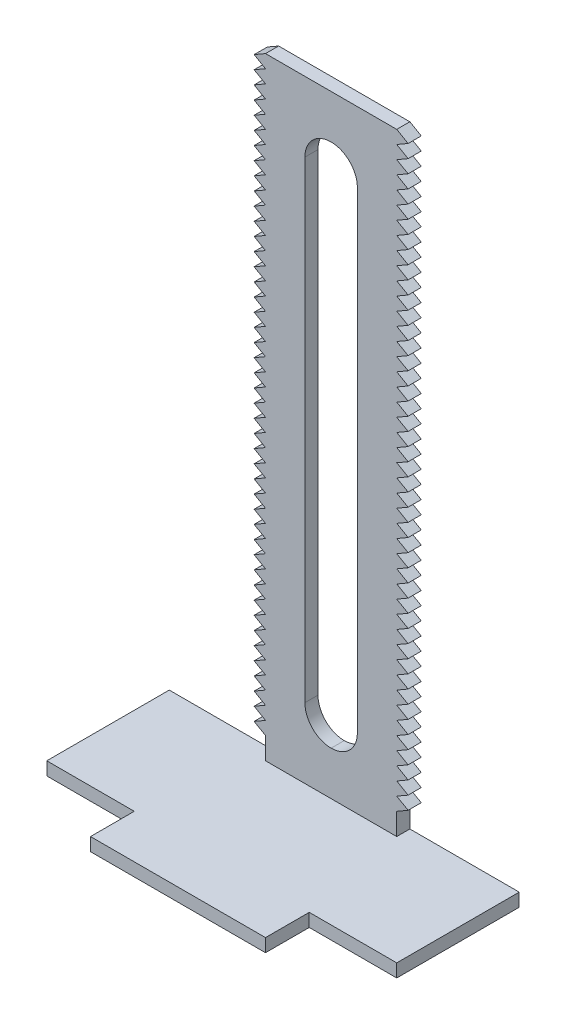
SolidWorks part; units mm, degrees
ref_plane "Front Plane" through (0, 0, 0) normal (0, 0, 1) x (1, 0, 0)
ref_plane "Top Plane" through (0, 0, 0) normal (0, 1, 0) x (1, 0, 0)
ref_plane "Right Plane" through (0, 0, 0) normal (1, 0, 0) x (0, 0, -1)
sketch "Sketch2" plane through (0, 0, 0) normal (0, 1, 0) x (1, 0, 0)
  line L1 (-15, 1.5) -> (15, 1.5)
  line L2 (-15, 1.5) -> (-15, -1.5)
  line L3 (-15, -1.5) -> (15, -1.5)
  line L4 (15, 1.5) -> (15, -1.5)
  line L5 (-15, 1.5) -> (15, -1.5) construction
  line L6 (-15, -1.5) -> (15, 1.5) construction
  point P0 (0, 0)
  dimension "D1" = 30
  dimension "D2" = 3
extrude "Boss-Extrude1" add sketch "Sketch2" along normal blind 110
sketch "Sketch3" plane through (0, 0, 1.5) normal (0, 0, 1) x (1, 0, 0)
  line L0 (15, 110) -> (17.5981, 108.5)
  line L1 (17.5981, 108.5) -> (15, 107)
  line L2 (15, 110) -> (15, 0) construction
  line L3 (15, 107) -> (15, 110)
  line L4 (15, 110) -> (15, 107)
  line L5 (15, 104) -> (15, 107)
  line L6 (17.5981, 105.5) -> (15, 104)
  line L7 (15, 107) -> (17.5981, 105.5)
  line L8 (15, 101) -> (15, 104)
  line L9 (17.5981, 102.5) -> (15, 101)
  line L10 (15, 104) -> (17.5981, 102.5)
  line L11 (15, 98) -> (15, 101)
  line L12 (17.5981, 99.5) -> (15, 98)
  line L13 (15, 101) -> (17.5981, 99.5)
  line L14 (15, 95) -> (15, 98)
  line L15 (17.5981, 96.5) -> (15, 95)
  line L16 (15, 98) -> (17.5981, 96.5)
  line L17 (15, 92) -> (15, 95)
  line L18 (17.5981, 93.5) -> (15, 92)
  line L19 (15, 95) -> (17.5981, 93.5)
  line L20 (15, 89) -> (15, 92)
  line L21 (17.5981, 90.5) -> (15, 89)
  line L22 (15, 92) -> (17.5981, 90.5)
  line L23 (15, 86) -> (15, 89)
  line L24 (17.5981, 87.5) -> (15, 86)
  line L25 (15, 89) -> (17.5981, 87.5)
  line L26 (15, 83) -> (15, 86)
  line L27 (17.5981, 84.5) -> (15, 83)
  line L28 (15, 86) -> (17.5981, 84.5)
  line L29 (15, 80) -> (15, 83)
  line L30 (17.5981, 81.5) -> (15, 80)
  line L31 (15, 83) -> (17.5981, 81.5)
  line L32 (15, 77) -> (15, 80)
  line L33 (17.5981, 78.5) -> (15, 77)
  line L34 (15, 80) -> (17.5981, 78.5)
  line L35 (15, 74) -> (15, 77)
  line L36 (17.5981, 75.5) -> (15, 74)
  line L37 (15, 77) -> (17.5981, 75.5)
  line L38 (15, 71) -> (15, 74)
  line L39 (17.5981, 72.5) -> (15, 71)
  line L40 (15, 74) -> (17.5981, 72.5)
  line L41 (15, 68) -> (15, 71)
  line L42 (17.5981, 69.5) -> (15, 68)
  line L43 (15, 71) -> (17.5981, 69.5)
  line L44 (15, 65) -> (15, 68)
  line L45 (17.5981, 66.5) -> (15, 65)
  line L46 (15, 68) -> (17.5981, 66.5)
  line L47 (15, 62) -> (15, 65)
  line L48 (17.5981, 63.5) -> (15, 62)
  line L49 (15, 65) -> (17.5981, 63.5)
  line L50 (15, 59) -> (15, 62)
  line L51 (17.5981, 60.5) -> (15, 59)
  line L52 (15, 62) -> (17.5981, 60.5)
  line L53 (15, 56) -> (15, 59)
  line L54 (17.5981, 57.5) -> (15, 56)
  line L55 (15, 59) -> (17.5981, 57.5)
  line L56 (15, 53) -> (15, 56)
  line L57 (17.5981, 54.5) -> (15, 53)
  line L58 (15, 56) -> (17.5981, 54.5)
  line L59 (15, 50) -> (15, 53)
  line L60 (17.5981, 51.5) -> (15, 50)
  line L61 (15, 53) -> (17.5981, 51.5)
  line L62 (15, 47) -> (15, 50)
  line L63 (17.5981, 48.5) -> (15, 47)
  line L64 (15, 50) -> (17.5981, 48.5)
  line L65 (15, 44) -> (15, 47)
  line L66 (17.5981, 45.5) -> (15, 44)
  line L67 (15, 47) -> (17.5981, 45.5)
  line L68 (15, 41) -> (15, 44)
  line L69 (17.5981, 42.5) -> (15, 41)
  line L70 (15, 44) -> (17.5981, 42.5)
  line L71 (15, 38) -> (15, 41)
  line L72 (17.5981, 39.5) -> (15, 38)
  line L73 (15, 41) -> (17.5981, 39.5)
  line L74 (15, 35) -> (15, 38)
  line L75 (17.5981, 36.5) -> (15, 35)
  line L76 (15, 38) -> (17.5981, 36.5)
  line L77 (-15, 110) -> (-15, 0) construction
  line L78 (-15, 110) -> (-17.5981, 108.5)
  line L79 (-17.5981, 108.5) -> (-15, 107)
  line L80 (-15, 107) -> (-15, 110)
  line L81 (-17.5981, 105.5) -> (-15, 104)
  line L82 (-15, 107) -> (-17.5981, 105.5)
  line L83 (-15, 104) -> (-15, 107)
  line L84 (-17.5981, 102.5) -> (-15, 101)
  line L85 (-15, 104) -> (-17.5981, 102.5)
  line L86 (-15, 101) -> (-15, 104)
  line L87 (-17.5981, 99.5) -> (-15, 98)
  line L88 (-15, 101) -> (-17.5981, 99.5)
  line L89 (-15, 98) -> (-15, 101)
  line L90 (-17.5981, 96.5) -> (-15, 95)
  line L91 (-15, 98) -> (-17.5981, 96.5)
  line L92 (-15, 95) -> (-15, 98)
  line L93 (-17.5981, 93.5) -> (-15, 92)
  line L94 (-15, 95) -> (-17.5981, 93.5)
  line L95 (-15, 92) -> (-15, 95)
  line L96 (-17.5981, 90.5) -> (-15, 89)
  line L97 (-15, 92) -> (-17.5981, 90.5)
  line L98 (-15, 89) -> (-15, 92)
  line L99 (-17.5981, 87.5) -> (-15, 86)
  line L100 (-15, 89) -> (-17.5981, 87.5)
  line L101 (-15, 86) -> (-15, 89)
  line L102 (-17.5981, 84.5) -> (-15, 83)
  line L103 (-15, 86) -> (-17.5981, 84.5)
  line L104 (-15, 83) -> (-15, 86)
  line L105 (-17.5981, 81.5) -> (-15, 80)
  line L106 (-15, 83) -> (-17.5981, 81.5)
  line L107 (-15, 80) -> (-15, 83)
  line L108 (-17.5981, 78.5) -> (-15, 77)
  line L109 (-15, 80) -> (-17.5981, 78.5)
  line L110 (-15, 77) -> (-15, 80)
  line L111 (-17.5981, 75.5) -> (-15, 74)
  line L112 (-15, 77) -> (-17.5981, 75.5)
  line L113 (-15, 74) -> (-15, 77)
  line L114 (-17.5981, 72.5) -> (-15, 71)
  line L115 (-15, 74) -> (-17.5981, 72.5)
  line L116 (-15, 71) -> (-15, 74)
  line L117 (-17.5981, 69.5) -> (-15, 68)
  line L118 (-15, 71) -> (-17.5981, 69.5)
  line L119 (-15, 68) -> (-15, 71)
  line L120 (-17.5981, 66.5) -> (-15, 65)
  line L121 (-15, 68) -> (-17.5981, 66.5)
  line L122 (-15, 65) -> (-15, 68)
  line L123 (-17.5981, 63.5) -> (-15, 62)
  line L124 (-15, 65) -> (-17.5981, 63.5)
  line L125 (-15, 62) -> (-15, 65)
  line L126 (-17.5981, 60.5) -> (-15, 59)
  line L127 (-15, 62) -> (-17.5981, 60.5)
  line L128 (-15, 59) -> (-15, 62)
  line L129 (-17.5981, 57.5) -> (-15, 56)
  line L130 (-15, 59) -> (-17.5981, 57.5)
  line L131 (-15, 56) -> (-15, 59)
  line L132 (-17.5981, 54.5) -> (-15, 53)
  line L133 (-15, 56) -> (-17.5981, 54.5)
  line L134 (-15, 53) -> (-15, 56)
  line L135 (-17.5981, 51.5) -> (-15, 50)
  line L136 (-15, 53) -> (-17.5981, 51.5)
  line L137 (-15, 50) -> (-15, 53)
  line L138 (-17.5981, 48.5) -> (-15, 47)
  line L139 (-15, 50) -> (-17.5981, 48.5)
  line L140 (-15, 47) -> (-15, 50)
  line L141 (-17.5981, 45.5) -> (-15, 44)
  line L142 (-15, 47) -> (-17.5981, 45.5)
  line L143 (-15, 44) -> (-15, 47)
  line L144 (-17.5981, 42.5) -> (-15, 41)
  line L145 (-15, 44) -> (-17.5981, 42.5)
  line L146 (-15, 41) -> (-15, 44)
  line L147 (-17.5981, 39.5) -> (-15, 38)
  line L148 (-15, 41) -> (-17.5981, 39.5)
  line L149 (-15, 38) -> (-15, 41)
  line L150 (-17.5981, 36.5) -> (-15, 35)
  line L151 (-15, 38) -> (-17.5981, 36.5)
  line L152 (-15, 35) -> (-15, 38)
  line L153 (-17.5981, 33.5) -> (-15, 32)
  line L154 (-15, 35) -> (-17.5981, 33.5)
  line L155 (-15, 32) -> (-15, 35)
  line L156 (17.5981, 33.5) -> (15, 32)
  line L157 (15, 32) -> (15, 35)
  line L158 (15, 35) -> (17.5981, 33.5)
  line L159 (-17.5981, 30.5) -> (-15, 29)
  line L160 (-15, 32) -> (-17.5981, 30.5)
  line L161 (-15, 29) -> (-15, 32)
  line L162 (17.5981, 30.5) -> (15, 29)
  line L163 (15, 29) -> (15, 32)
  line L164 (15, 32) -> (17.5981, 30.5)
  line L165 (-17.5981, 27.5) -> (-15, 26)
  line L166 (-15, 29) -> (-17.5981, 27.5)
  line L167 (-15, 26) -> (-15, 29)
  line L168 (17.5981, 27.5) -> (15, 26)
  line L169 (15, 26) -> (15, 29)
  line L170 (15, 29) -> (17.5981, 27.5)
  line L171 (-17.5981, 24.5) -> (-15, 23)
  line L172 (-15, 26) -> (-17.5981, 24.5)
  line L173 (-15, 23) -> (-15, 26)
  line L174 (17.5981, 24.5) -> (15, 23)
  line L175 (15, 23) -> (15, 26)
  line L176 (15, 26) -> (17.5981, 24.5)
  line L177 (-17.5981, 21.5) -> (-15, 20)
  line L178 (-15, 23) -> (-17.5981, 21.5)
  line L179 (-15, 20) -> (-15, 23)
  line L180 (17.5981, 21.5) -> (15, 20)
  line L181 (15, 20) -> (15, 23)
  line L182 (15, 23) -> (17.5981, 21.5)
  line L183 (-17.5981, 18.5) -> (-15, 17)
  line L184 (-15, 20) -> (-17.5981, 18.5)
  line L185 (-15, 17) -> (-15, 20)
  line L186 (17.5981, 18.5) -> (15, 17)
  line L187 (15, 17) -> (15, 20)
  line L188 (15, 20) -> (17.5981, 18.5)
  line L189 (-17.5981, 15.5) -> (-15, 14)
  line L190 (-15, 17) -> (-17.5981, 15.5)
  line L191 (-15, 14) -> (-15, 17)
  line L192 (17.5981, 15.5) -> (15, 14)
  line L193 (15, 14) -> (15, 17)
  line L194 (15, 17) -> (17.5981, 15.5)
  line L195 (-17.5981, 12.5) -> (-15, 11)
  line L196 (-15, 14) -> (-17.5981, 12.5)
  line L197 (-15, 11) -> (-15, 14)
  line L198 (17.5981, 12.5) -> (15, 11)
  line L199 (15, 11) -> (15, 14)
  line L200 (15, 14) -> (17.5981, 12.5)
  line L201 (-17.5981, 9.5) -> (-15, 8)
  line L202 (-15, 11) -> (-17.5981, 9.5)
  line L203 (-15, 8) -> (-15, 11)
  line L204 (17.5981, 9.5) -> (15, 8)
  line L205 (15, 8) -> (15, 11)
  line L206 (15, 11) -> (17.5981, 9.5)
  line L207 (-17.5981, 6.5) -> (-15, 5)
  line L208 (-15, 8) -> (-17.5981, 6.5)
  line L209 (-15, 5) -> (-15, 8)
  line L210 (17.5981, 6.5) -> (15, 5)
  line L211 (15, 5) -> (15, 8)
  line L212 (15, 8) -> (17.5981, 6.5)
  line M152 (15, 0) -> (15, 110)
  line M154 (-15, 110) -> (-15, 0)
  dimension "D1" = 3
  dimension "D2" = 3
  dimension "D3" = 3
  dimension "D5" = 30
  dimension "D6" = 2.5981
  dimension "D7" = 3
  dimension "D8" = 3
  dimension "D9" = 3
  dimension "D11" = 30
  dimension "D12" = 2.5981
  dimension "D14" = 2.5981
  dimension "D4" = 25
  dimension "D10" = 25
  dimension "D13" = 11
extrude "Boss-Extrude2" add sketch "Sketch3" against normal blind 3 contours L78 L79 M154 | L82 L81 M154 | L85 L84 M154 | L88 L87 M154 | L91 L90 M154 | L94 L93 M154 | L97 L96 M154 | L100 L99 M154 | L103 L102 M154 | L106 L105 M154 | L109 L108 M154 | L1 L0 M152 | L7 L6 M152 | L10 L9 M152 | L13 L12 M152 | L16 L15 M152 | L19 L18 M152 | L22 L21 M152 | L25 L24 M152 | L28 L27 M152 | L31 L30 M152 | L34 L33 M152 | L112 L111 M154 | L115 L114 M154 | L118 L117 M154 | L121 L120 M154 | L124 L123 M154 | L127 L126 M154 | L130 L129 M154 | L133 L132 M154 | L136 L135 M154 | L139 L138 M154 | L142 L141 M154 | L145 L144 M154 | L148 L147 M154 | L151 L150 M154 | L37 L36 M152 | L43 L42 M152 | L46 L45 M152 | L49 L48 M152 | L61 L60 M152 | L64 L63 M152 | L67 L66 M152 | L70 L69 M152 | L73 L72 M152 | L158 L156 M152 | L164 L162 M152 | L154 L153 M154 | L160 L159 M154 | L166 L165 M154 | L172 L171 M154 | L178 L177 M154 | L184 L183 M154 | L170 L168 M152 | L176 L174 M152 | L190 L189 M154 | L182 L180 M152 | L188 L186 M152 | L196 L195 M154 | L194 L192 M152 | L200 L198 M152 | L206 L204 M152 | L212 L210 M152 | L208 L207 M154 | L202 L201 M154 | L40 L39 L38 | L52 L51 L50 | L55 L54 L53 | L58 L57 L56 | L76 L75 L74 region at (15.866, 6.5, 1.5) region at (15.866, 9.5, 1.5) region at (15.866, 12.5, 1.5) region at (15.866, 15.5, 1.5) region at (15.866, 18.5, 1.5) region at (15.866, 21.5, 1.5) region at (15.866, 24.5, 1.5) region at (15.866, 27.5, 1.5) region at (15.866, 30.5, 1.5) region at (15.866, 33.5, 1.5) region at (15.866, 39.5, 1.5) region at (15.866, 42.5, 1.5) region at (15.866, 45.5, 1.5) region at (15.866, 48.5, 1.5) region at (15.866, 51.5, 1.5) region at (15.866, 63.5, 1.5) region at (15.866, 66.5, 1.5) region at (15.866, 69.5, 1.5) region at (15.866, 75.5, 1.5) region at (15.866, 78.5, 1.5) region at (15.866, 81.5, 1.5) region at (15.866, 84.5, 1.5) region at (15.866, 87.5, 1.5) region at (15.866, 90.5, 1.5) region at (15.866, 93.5, 1.5) region at (15.866, 96.5, 1.5) region at (15.866, 99.5, 1.5) region at (15.866, 102.5, 1.5) region at (15.866, 105.5, 1.5) region at (15.866, 108.5, 1.5) region at (-15.866, 108.5, 1.5) region at (-15.866, 6.5, 1.5) region at (-15.866, 9.5, 1.5) region at (-15.866, 12.5, 1.5) region at (-15.866, 15.5, 1.5) region at (-15.866, 18.5, 1.5) region at (-15.866, 21.5, 1.5) region at (-15.866, 24.5, 1.5) region at (-15.866, 27.5, 1.5) region at (-15.866, 30.5, 1.5) region at (-15.866, 33.5, 1.5) region at (-15.866, 36.5, 1.5) region at (-15.866, 39.5, 1.5) region at (-15.866, 42.5, 1.5) region at (-15.866, 45.5, 1.5) region at (-15.866, 48.5, 1.5) region at (-15.866, 51.5, 1.5) region at (-15.866, 54.5, 1.5) region at (-15.866, 57.5, 1.5) region at (-15.866, 60.5, 1.5) region at (-15.866, 63.5, 1.5) region at (-15.866, 66.5, 1.5) region at (-15.866, 69.5, 1.5) region at (-15.866, 72.5, 1.5) region at (-15.866, 75.5, 1.5) region at (-15.866, 78.5, 1.5) region at (-15.866, 81.5, 1.5) region at (-15.866, 84.5, 1.5) region at (-15.866, 87.5, 1.5) region at (-15.866, 90.5, 1.5)
sketch "Sketch4" plane through (0, 0, 1.5) normal (0, 0, 1) x (1, 0, 0)
  line L0 (-9, 0) -> (-9, -3)
  line L1 (-15, 0) -> (15, 0)
  line L2 (-15, 0) -> (-15, -6)
  line L3 (-15, -6) -> (15, -6)
  line L4 (15, 0) -> (15, -6)
  line L5 (-15, 0) -> (-12, 0)
  line L6 (-15, 0) -> (-15, -3)
  line L7 (-15, -3) -> (-12, -3)
  line L8 (-12, 0) -> (-12, -3)
  line L9 (-12, -3) -> (-9, -3)
  line L10 (-6, 0) -> (-6, -3)
  line L11 (-9, -3) -> (-6, -3)
  line L12 (-3, 0) -> (-3, -3)
  line L13 (-6, -3) -> (-3, -3)
  line L14 (0, 0) -> (0, -3)
  line L15 (-3, -3) -> (0, -3)
  line L16 (3, 0) -> (3, -3)
  line L17 (0, -3) -> (3, -3)
  line L18 (6, 0) -> (6, -3)
  line L19 (3, -3) -> (6, -3)
  line L20 (9, 0) -> (9, -3)
  line L21 (6, -3) -> (9, -3)
  line L22 (12, 0) -> (12, -3)
  line L23 (9, -3) -> (12, -3)
  line L24 (15, 0) -> (15, -3)
  line L25 (12, -3) -> (15, -3)
  dimension "D1" = 6
  dimension "D2" = 30
  dimension "D3" = 3
  dimension "D4" = 3
  dimension "D6" = 6
  dimension "D7" = 3
  dimension "D5" = 10
extrude "Boss-Extrude3" add sketch "Sketch4" against normal blind 3 contours L25 L23 L21 L19 L17 L15 L13 L11 L9 L7 L2 L3 L4 | L8 L1 L2 L7 | L0 L11 L10 L1 | L12 L15 L14 L1 | L14 L17 L16 L1 | L18 L21 L20 L1 | L22 L25 L4 L1 region at (-7.5, -1.5, 1.5) region at (0, -4.5, 1.5) region at (-13.5, -1.5, 1.5) region at (-1.5, -1.5, 1.5) region at (1.5, -1.5, 1.5) region at (7.5, -1.5, 1.5) region at (13.5, -1.5, 1.5)
sketch "Sketch5" plane through (0, 0, -1.5) normal (0, 0, -1) x (-1, 0, 0)
  line L0 (-15, 5) -> (-15, -6) construction
  line L1 (-6, 100) -> (6, 100)
  line L2 (-6, 100) -> (-6, 10)
  line L3 (-6, 10) -> (6, 10)
  line L4 (6, 100) -> (6, 10)
  line L5 (15, -6) -> (-15, -6) construction
  dimension "D1" = 12
  dimension "D2" = 90
  dimension "D3" = 9
  dimension "D4" = 16
extrude "Cut-Extrude1" cut sketch "Sketch5" against normal blind 3
fillet "Fillet1" radius 6 4 edges at (-6, 10, 0) (6, 10, 0) (6, 100, 0) (-6, 100, 0)
sketch "Sketch7" plane through (0, 0, 1.5) normal (0, 0, 1) x (1, 0, 0)
  line L0 (-15, 5) -> (-15, -6) construction
  line L1 (-15, 0) -> (15, 0)
  line L2 (-15, 0) -> (-15, -3)
  line L3 (-15, -3) -> (15, -3)
  line L4 (15, 0) -> (15, -3)
  line L5 (15, 5) -> (15, -6) construction
  line L6 (-15, -6) -> (15, -6) construction
  line L8 (-15, 0) -> (-12, 0)
  line L9 (-15, 0) -> (-15, -3)
  line L10 (-15, -3) -> (-12, -3)
  line L11 (-12, 0) -> (-12, -3)
  line L12 (-12, -3) -> (-9, -3)
  line L13 (-12, -3) -> (-12, 0)
  line L14 (-12, 0) -> (-9, 0)
  line L15 (-9, -3) -> (-9, 0)
  line L16 (-9, 0) -> (-6, 0)
  line L17 (-9, 0) -> (-9, -3)
  line L18 (-9, -3) -> (-6, -3)
  line L19 (-6, 0) -> (-6, -3)
  line L20 (-6, -3) -> (-3, -3)
  line L21 (-6, -3) -> (-6, 0)
  line L22 (-6, 0) -> (-3, 0)
  line L23 (-3, -3) -> (-3, 0)
  line L24 (-3, 0) -> (3, 0)
  line L25 (-3, 0) -> (-3, -3)
  line L26 (-3, -3) -> (3, -3)
  line L27 (3, 0) -> (3, -3)
  line L28 (3, -3) -> (6, -3)
  line L29 (3, -3) -> (3, 0)
  line L30 (3, 0) -> (6, 0)
  line L31 (6, -3) -> (6, 0)
  line L32 (6, 0) -> (9, 0)
  line L33 (6, 0) -> (6, -3)
  line L34 (6, -3) -> (9, -3)
  line L35 (9, 0) -> (9, -3)
  line L36 (9, -3) -> (12, -3)
  line L37 (9, -3) -> (9, 0)
  line L38 (9, 0) -> (12, 0)
  line L39 (12, -3) -> (12, 0)
  line L40 (12, 0) -> (15, 0)
  line L41 (12, 0) -> (12, -3)
  line L42 (12, -3) -> (15, -3)
  line L43 (15, 0) -> (15, -3)
  dimension "D1" = 3
  dimension "D2" = 3
extrude "Boss-Extrude8" add sketch "Sketch7" along normal blind 10 contours L11 L1 L2 L3 | L19 L1 L15 L3 | L27 L1 L23 L3 | L35 L1 L31 L3 | L39 L3 L4 L1 region at (-13.5, -1.5, 1.5) region at (-7.5, -1.5, 1.5) region at (0, -1.5, 1.5) region at (7.5, -1.5, 1.5) region at (13.5, -1.5, 1.5)
sketch "Sketch8" plane through (-9, 0, 0) normal (-1, 0, 0) x (0, 0, 1)
  line L1 (-1.5, 0) -> (11.5, 0)
  line L2 (-1.5, 0) -> (-1.5, -3)
  line L3 (-1.5, -3) -> (11.5, -3)
  line L4 (11.5, 0) -> (11.5, -3)
extrude "Boss-Extrude9" add sketch "Sketch8" along normal blind 3
sketch "Sketch9" plane through (-3, 0, 0) normal (-1, 0, 0) x (0, 0, 1)
  line L1 (-1.5, 0) -> (11.5, 0)
  line L2 (-1.5, 0) -> (-1.5, -3)
  line L3 (-1.5, -3) -> (11.5, -3)
  line L4 (11.5, 0) -> (11.5, -3)
extrude "Boss-Extrude10" add sketch "Sketch9" along normal blind 3
sketch "Sketch10" plane through (6, 0, 0) normal (-1, 0, 0) x (0, 0, 1)
  line L1 (-1.5, 0) -> (11.5, 0)
  line L2 (-1.5, 0) -> (-1.5, -3)
  line L3 (-1.5, -3) -> (11.5, -3)
  line L4 (11.5, 0) -> (11.5, -3)
extrude "Boss-Extrude11" add sketch "Sketch10" along normal blind 3
sketch "Sketch11" plane through (12, 0, 0) normal (-1, 0, 0) x (0, 0, 1)
  line L1 (-1.5, 0) -> (11.5, 0)
  line L2 (-1.5, 0) -> (-1.5, -3)
  line L3 (-1.5, -3) -> (11.5, -3)
  line L4 (11.5, 0) -> (11.5, -3)
extrude "Boss-Extrude12" add sketch "Sketch11" along normal blind 3
sketch "Sketch12" plane through (-15, 0, 0) normal (-1, 0, 0) x (0, 0, 1)
  line L0 (-1.5, 5) -> (-1.5, -6) construction
  line L1 (11.5, 0) -> (-1.5, 0)
  line L2 (11.5, 0) -> (11.5, -3)
  line L3 (11.5, -3) -> (-1.5, -3)
  line L4 (-1.5, 0) -> (-1.5, -3)
  dimension "D1" = 3
extrude "Boss-Extrude13" add sketch "Sketch12" along normal blind 25
sketch "Sketch13" plane through (15, 0, 0) normal (1, 0, 0) x (0, 0, -1)
  line L0 (1.5, 5) -> (1.5, -6) construction
  line L1 (-11.5, 0) -> (1.5, 0)
  line L2 (-11.5, 0) -> (-11.5, -3)
  line L3 (-11.5, -3) -> (1.5, -3)
  line L4 (1.5, 0) -> (1.5, -3)
  dimension "D1" = 3
extrude "Boss-Extrude14" add sketch "Sketch13" along normal blind 25
sketch "Sketch14" plane through (0, 0, 11.5) normal (0, 0, 1) x (1, 0, 0)
  line L1 (-40, 0) -> (40, 0)
  line L2 (-40, 0) -> (-40, -3)
  line L3 (-40, -3) -> (40, -3)
  line L4 (40, 0) -> (40, -3)
extrude "Boss-Extrude15" add sketch "Sketch14" along normal blind 25
sketch "Sketch15" plane through (0, -3, 0) normal (0, -1, 0) x (1, 0, 0)
  line L0 (-40, 36.5) -> (40, 36.5) construction
  line L1 (-33, 36.5) -> (-30, 36.5)
  line L2 (-33, 36.5) -> (-33, -1.5)
  line L3 (-33, -1.5) -> (-30, -1.5)
  line L4 (-30, 36.5) -> (-30, -1.5)
  line L5 (-40, -1.5) -> (-15, -1.5) construction
  line L6 (-15, -1.5) -> (-15, 1.5) construction
  dimension "D1" = 3
  dimension "D2" = 15
extrude "Boss-Extrude16" add sketch "Sketch15" along normal blind 40
sketch "Sketch16" plane through (0, -3, 0) normal (0, -1, 0) x (1, 0, 0)
  line L0 (40, 36.5) -> (40, -1.5) construction
  line L1 (40, 20) -> (20, 20)
  line L2 (40, 20) -> (40, 15)
  line L3 (40, 15) -> (20, 15)
  line L4 (20, 20) -> (20, 15)
  line L7 (40, -1.5) -> (15, -1.5) construction
  dimension "D1" = 5
  dimension "D2" = 20
  dimension "D3" = 16.5
extrude "Cut-Extrude2" cut sketch "Sketch16" against normal blind 3
sketch "Sketch17" plane through (-30, 0, 0) normal (1, 0, 0) x (0, 0, -1)
  line L1 (-36.5, -43) -> (1.5, -43)
  line L2 (-36.5, -43) -> (-36.5, -3)
  line L3 (-36.5, -3) -> (1.5, -3)
  line L4 (1.5, -43) -> (1.5, -3)
extrude "Cut-Extrude3" cut sketch "Sketch17" against normal blind 3
sketch "Sketch19" plane through (0, 0, 1.5) normal (0, 0, 1) x (1, 0, 0)
  line L1 (-15, -3) -> (15, -3)
  line L2 (-15, -3) -> (-15, -6)
  line L3 (-15, -6) -> (15, -6)
  line L4 (15, -3) -> (15, -6)
extrude "Cut-Extrude4" cut sketch "Sketch19" against normal blind 3
sketch "Sketch20" plane through (20, 0, 0) normal (1, 0, 0) x (0, 0, -1)
  line L0 (-20, 0) -> (-15, 0) construction
  line L1 (-20, -3) -> (-15, -3)
  line L2 (-20, -3) -> (-20, 0)
  line L3 (-20, 0) -> (-15, 0)
  line L4 (-15, -3) -> (-15, 0)
extrude "Boss-Extrude17" add sketch "Sketch20" along normal up to surface (20 mm away) up to face at (40, -1.5, 28.25)
sketch "Sketch21" plane through (0, -3, 0) normal (0, -1, 0) x (-1, 0, 0)
  line L1 (40, -36.5) -> (20, -36.5)
  line L2 (40, -36.5) -> (40, -26.5)
  line L3 (40, -26.5) -> (20, -26.5)
  line L4 (20, -36.5) -> (20, -26.5)
  line L5 (-40, -36.5) -> (-20, -36.5)
  line L6 (-40, -36.5) -> (-40, -26.5)
  line L7 (-40, -26.5) -> (-20, -26.5)
  line L8 (-20, -36.5) -> (-20, -26.5)
  dimension "D1" = 20
  dimension "D2" = 10
  dimension "D3" = 20
  dimension "D4" = 10
extrude "Cut-Extrude5" cut sketch "Sketch21" against normal blind 3
sketch "Sketch22" plane through (0, 110, 0) normal (0, 1, 0) x (1, 0, 0)
  line L1 (-15, 1.5) -> (15, 1.5)
  line L2 (-15, 1.5) -> (-15, -1.5)
  line L3 (-15, -1.5) -> (15, -1.5)
  line L4 (15, 1.5) -> (15, -1.5)
extrude "Boss-Extrude18" add sketch "Sketch22" along normal blind 30
sketch "Sketch23" plane through (0, 0, 1.5) normal (0, 0, 1) x (1, 0, 0)
  line L0 (-15, 110) -> (-17.5981, 111.5)
  line L1 (-17.5981, 111.5) -> (-15, 113)
  line L2 (-15, 140) -> (-15, 110) construction
  line L3 (-15, 110) -> (-15, 113)
  line L4 (-17.5981, 114.5) -> (-15, 116)
  line L5 (-15, 113) -> (-17.5981, 114.5)
  line L6 (-15, 113) -> (-15, 116)
  line L7 (-17.5981, 117.5) -> (-15, 119)
  line L8 (-15, 116) -> (-17.5981, 117.5)
  line L9 (-15, 116) -> (-15, 119)
  line L10 (-17.5981, 120.5) -> (-15, 122)
  line L11 (-15, 119) -> (-17.5981, 120.5)
  line L12 (-15, 119) -> (-15, 122)
  line L13 (-17.5981, 123.5) -> (-15, 125)
  line L14 (-15, 122) -> (-17.5981, 123.5)
  line L15 (-15, 122) -> (-15, 125)
  line L16 (-17.5981, 126.5) -> (-15, 128)
  line L17 (-15, 125) -> (-17.5981, 126.5)
  line L18 (-15, 125) -> (-15, 128)
  line L19 (-17.5981, 129.5) -> (-15, 131)
  line L20 (-15, 128) -> (-17.5981, 129.5)
  line L21 (-15, 128) -> (-15, 131)
  line L22 (-17.5981, 132.5) -> (-15, 134)
  line L23 (-15, 131) -> (-17.5981, 132.5)
  line L24 (-15, 131) -> (-15, 134)
  line L25 (-17.5981, 135.5) -> (-15, 137)
  line L26 (-15, 134) -> (-17.5981, 135.5)
  line L27 (-15, 134) -> (-15, 137)
  line L28 (-17.5981, 138.5) -> (-15, 140)
  line L29 (-15, 137) -> (-17.5981, 138.5)
  line L30 (-15, 137) -> (-15, 140)
  line L32 (0, 100) -> (0, 140)
  line L33 (-15, 140) -> (15, 140) construction
  line L34 (15, 134) -> (15, 137)
  line L35 (17.5981, 135.5) -> (15, 137)
  line L36 (15, 110) -> (17.5981, 111.5)
  line L37 (17.5981, 111.5) -> (15, 113)
  line L38 (15, 110) -> (15, 113)
  line L39 (15, 113) -> (17.5981, 114.5)
  line L40 (17.5981, 114.5) -> (15, 116)
  line L41 (15, 116) -> (17.5981, 117.5)
  line L42 (17.5981, 117.5) -> (15, 119)
  line L43 (15, 119) -> (17.5981, 120.5)
  line L44 (17.5981, 120.5) -> (15, 122)
  line L45 (15, 134) -> (17.5981, 135.5)
  line L46 (15, 131) -> (15, 134)
  line L47 (15, 131) -> (17.5981, 132.5)
  line L48 (17.5981, 132.5) -> (15, 134)
  line L49 (15, 128) -> (15, 131)
  line L50 (15, 128) -> (17.5981, 129.5)
  line L51 (17.5981, 129.5) -> (15, 131)
  line L52 (15, 125) -> (15, 128)
  line L53 (15, 125) -> (17.5981, 126.5)
  line L54 (17.5981, 126.5) -> (15, 128)
  line L55 (15, 122) -> (15, 125)
  line L56 (15, 122) -> (17.5981, 123.5)
  line L57 (17.5981, 123.5) -> (15, 125)
  line L58 (15, 119) -> (15, 122)
  line L59 (15, 116) -> (15, 119)
  line L60 (15, 113) -> (15, 116)
  line L61 (15, 137) -> (15, 140)
  line L62 (15, 137) -> (17.5981, 138.5)
  line L63 (17.5981, 138.5) -> (15, 140)
  dimension "D1" = 3
  dimension "D2" = 3
  dimension "D3" = 3
  dimension "D4" = 10
extrude "Boss-Extrude19" add sketch "Sketch23" against normal blind 3 contours L29 L30 L28 | L26 L27 L25 | L23 L24 L22 | L20 L21 L19 | L17 L18 L16 | L14 L15 L13 | L11 L12 L10 | L8 L9 L7 | L5 L6 L4 | L0 L3 L1 | L62 L63 L61 | L34 L45 L35 | L47 L48 L46 | L50 L51 L49 | L53 L54 L52 | L56 L57 L55 | L58 L43 L44 | L59 L41 L42 | L60 L39 L40 | L38 L36 L37 region at (-15.866, 138.5, 1.5) region at (-15.866, 135.5, 1.5) region at (-15.866, 132.5, 1.5) region at (-15.866, 129.5, 1.5) region at (-15.866, 126.5, 1.5) region at (-15.866, 123.5, 1.5) region at (-15.866, 120.5, 1.5) region at (-15.866, 117.5, 1.5) region at (-15.866, 114.5, 1.5) region at (-15.866, 111.5, 1.5) region at (15.866, 138.5, 1.5) region at (15.866, 135.5, 1.5) region at (15.866, 132.5, 1.5) region at (15.866, 111.5, 1.5) region at (15.866, 114.5, 1.5) region at (15.866, 117.5, 1.5) region at (15.866, 120.5, 1.5) region at (15.866, 123.5, 1.5) region at (15.866, 126.5, 1.5) region at (15.866, 129.5, 1.5)
sketch "Sketch24" plane through (0, 0, 1.5) normal (0, 0, 1) x (1, 0, 0)
  line L0 (6, 94) -> (6, 16) construction
  line L1 (-6, 94) -> (6, 94)
  line L2 (-6, 94) -> (-6, 130)
  line L3 (-6, 130) -> (6, 130)
  line L4 (6, 94) -> (6, 130)
  circle A0 centre (0, 124) radius 6
  dimension "D3" = 12
  dimension "D4" = 6
  dimension "D5" = 6
  dimension "D1" = 36
  dimension "D2" = 0
extrude "Cut-Extrude7" cut sketch "Sketch24" against normal blind 3 contours A0 | A0 L2 L1 L4 region at (0, 106.6793, 1.5) region at (0, 124, 1.5)
